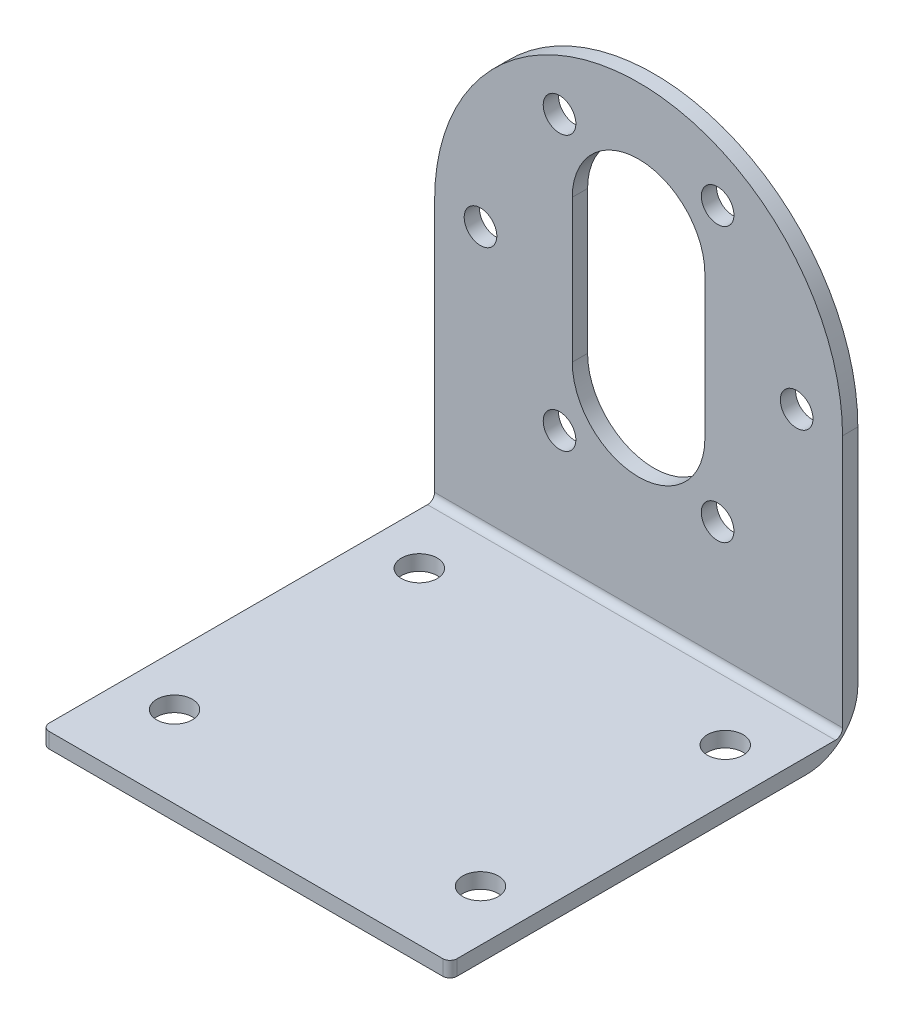
SolidWorks part; units mm, degrees
ref_plane "Front Plane" through (0, 0, 0) normal (0, 0, 1) x (1, 0, 0)
ref_plane "Top Plane" through (0, 0, 0) normal (0, 1, 0) x (1, 0, 0)
ref_plane "Right Plane" through (0, 0, 0) normal (1, 0, 0) x (0, 0, -1)
sketch "Sketch1" plane through (0, 0, 0) normal (1, 0, 0) x (0, 0, -1)
  line L0 (0, 1.5) -> (0, 0)
  line L1 (0, 0) -> (34.9633, 0)
  line L2 (40, 5.0367) -> (40, 47)
  line L3 (40, 47) -> (38.5, 47)
  line L4 (38.5, 47) -> (38.5, 1.5)
  line L5 (38.5, 1.5) -> (0, 1.5)
  arc A0 (34.9633, 0) -> (40, 5.0367) centre (34.9633, 5.0367) ccw
  point P8 (0, 0)
  point P9 (0, 0)
  point P10 (0, 0)
  point P12 (27.3, 4)
  point P13 (0, 0)
  dimension "D1" = 1.5
  dimension "D2" = 47
  dimension "D3" = 40
extrude "MainPiece" add sketch "Sketch1" along normal blind 40
sketch "Sketch2" plane through (0, 0, 0) normal (0, -1, 0) x (-1, 0, 0)
  line L6 (-5, 8) -> (-5, 32) construction
  line L7 (-5, 32) -> (-35, 32) construction
  line L8 (-35, 32) -> (-35, 8) construction
  line L9 (-35, 8) -> (-5, 8) construction
  line L11 (-40, 0) -> (0, 0) construction
  line L12 (0, 0) -> (0, 34.9633) construction
  circle A1 centre (-5, 8) radius 1.75
  circle A2 centre (-35, 8) radius 1.75
  circle A3 centre (-35, 32) radius 1.75
  circle A4 centre (-5, 32) radius 1.75
  point P4 (-24.3347, 8)
  point P6 (-6.5222, 32)
  point P18 (0, 0)
  point P19 (0, 0)
  point P20 (0, 0)
  point P21 (0, 0)
  point P22 (0, 0)
  dimension "D1" = 3.5
  dimension "D2" = 8
  dimension "D3" = 5
  dimension "D4" = 30
  dimension "D5" = 24
extrude "ChassisHoles" cut sketch "Sketch2" against normal up to next
sketch "Sketch3" plane through (0, 0, -40) normal (0, 0, -1) x (-1, 0, 0)
  line L1 (-40, 47) -> (0, 47) construction
  line L2 (-40, 5.0367) -> (-40, 47) construction
  line L3 (-40, 27) -> (-40, 47)
  line L4 (-40, 47) -> (0, 47)
  line L5 (0, 47) -> (0, 27)
  line L6 (0, 5.0367) -> (0, 47) construction
  arc A0 (0, 27) -> (-40, 27) centre (-20, 27) ccw
  point P3 (-20, 47)
  point P9 (0, 0)
  point P11 (0, 0)
  point P12 (0, 0)
  point P13 (0, 0)
  point P14 (0, 0)
  point P17 (3.9628, 33.5)
  point P18 (-29.7609, 33.5)
  line M3 (0, 5.0367) -> (0, 47)
  line M4 (0, 47) -> (-40, 47)
  line M5 (-40, 47) -> (-40, 5.0367)
extrude "Dome" cut sketch "Sketch3" against normal up to next contours A0 L4 M5 | A0 M3 M4 region at (4.4674, 42.5326, -40) region at (35.5326, 42.5326, -40)
sketch "Sketch4" plane through (0, 0, -40) normal (0, 0, -1) x (-1, 0, 0)
  line L0 (-26.5, 20) -> (-26.5, 34)
  line L1 (-20, 34) -> (-20, 47) construction
  line L2 (-13.5, 34) -> (-13.5, 20)
  line L3 (-20, 27) -> (-35.5002, 27) construction
  line L4 (-20, 34) -> (-20, 20) construction
  arc A3 (0, 27) -> (-40, 27) centre (-20, 27) ccw construction
  circle A4 centre (-35.5002, 27) radius 1.6
  arc A5 (-26.5, 34) -> (-13.5, 34) centre (-20, 34) cw
  arc A6 (-13.5, 20) -> (-26.5, 20) centre (-20, 20) cw
  circle A7 centre (-27.7501, 40.4235) radius 1.6
  circle A8 centre (-12.2499, 40.4235) radius 1.6
  circle A9 centre (-4.4998, 27) radius 1.6
  circle A10 centre (-12.2499, 13.5765) radius 1.6
  circle A11 centre (-27.7501, 13.5765) radius 1.6
  point P10 (0, 0)
  point P14 (-20, 47)
  point P29 (0, 0)
  point P30 (0, 0)
  point P31 (0, 0)
  point P32 (5.8398, 34)
  dimension "D3" = 14
  dimension "D4" = 3.2
  dimension "D2" = 6.5
  dimension "D1" = 13
  dimension "D6" = 15.5002
  dimension "D7" = 20
  dimension "D5" = 6
extrude "WheelMotorGuide" cut sketch "Sketch4" against normal up to next
fillet "Fillet1" radius 0.7 3 edges at (0, 0.75, 0) (40, 0.75, 0) (20, 1.5, -38.5)
